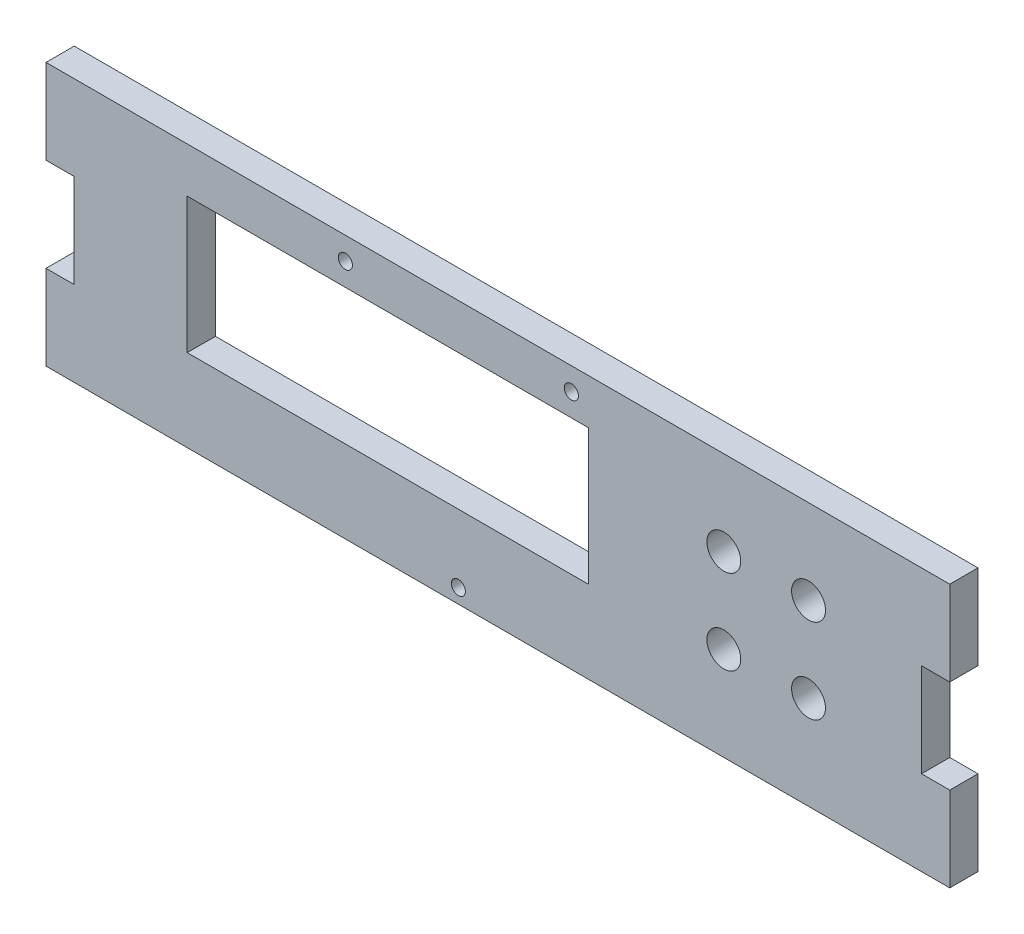
SolidWorks part; units mm, degrees
ref_plane "Plan de face" through (0, 0, 0) normal (0, 0, 1) x (1, 0, 0)
ref_plane "Plan de dessus" through (0, 0, 0) normal (0, 1, 0) x (1, 0, 0)
ref_plane "Plan de droite" through (0, 0, 0) normal (1, 0, 0) x (0, 0, -1)
sketch "Esquisse1" plane through (0, 0, 0) normal (0, 0, 1) x (1, 0, 0)
  line L0 (-79.9049, -61.6513) -> (-79.9049, -46.6513)
  line L1 (-79.9049, -46.6513) -> (80.0951, -46.6513)
  line L3 (-79.9049, -93.2213) -> (80.0951, -93.2213)
  line L5 (-79.9049, -61.6513) -> (-74.9049, -61.6513)
  line L7 (-79.9049, -78.2213) -> (-74.9049, -78.2213)
  line L8 (-74.9049, -61.6513) -> (-74.9049, -78.2213)
  line L9 (80.0951, -61.6513) -> (75.0951, -61.6513)
  line L11 (80.0951, -78.2213) -> (75.0951, -78.2213)
  line L12 (75.0951, -61.6513) -> (75.0951, -78.2213)
  line L13 (-79.9049, -78.2213) -> (-79.9049, -93.2213)
  line L14 (80.0951, -93.2213) -> (80.0951, -78.2213)
  line L15 (80.0951, -61.6513) -> (80.0951, -46.6513)
  line L17 (-54.9049, -54.6513) -> (16.0951, -54.6513)
  line L18 (-54.9049, -54.6513) -> (-54.9049, -78.6513)
  line L19 (-54.9049, -78.6513) -> (16.0951, -78.6513)
  line L20 (16.0951, -54.6513) -> (16.0951, -78.6513)
  circle A0 centre (40.0951, -61.6513) radius 3
  circle A1 centre (40.0951, -76.6513) radius 3
  circle A2 centre (55.0951, -61.6513) radius 3
  circle A3 centre (55.0951, -76.6513) radius 3
  circle A4 centre (13.0951, -50.6513) radius 1.25
  circle A5 centre (-26.9049, -50.6513) radius 1.25
  circle A6 centre (-6.9049, -90.6513) radius 1.25
  point P20 (80.0951, -54.1513)
  dimension "D1" = 6
  dimension "D9" = 6
  dimension "D10" = 6
  dimension "D11" = 6
  dimension "D22" = 2.5
  dimension "D25" = 2.5
  dimension "D28" = 2.5
  dimension "D2" = 15
  dimension "D3" = 20
  dimension "D4" = 15
  dimension "D5" = 16.57
  dimension "D6" = 15
  dimension "D7" = 15
  dimension "D8" = 16.57
  dimension "D12" = 0
  dimension "D13" = 71
  dimension "D14" = 160
  dimension "D15" = 0
  dimension "D16" = 15
  dimension "D17" = 15
  dimension "D18" = 0
  dimension "D19" = 24
  dimension "D20" = 20
  dimension "D21" = 8
  dimension "D23" = 3
  dimension "D24" = 4
  dimension "D26" = 4
  dimension "D27" = 40
  dimension "D29" = 12
  dimension "D30" = 23
extrude "Boss.-Extru.2" add sketch "Esquisse1" along normal blind 5 contours L0 L1 L15 L9 L12 L11 L14 L3 L13 L7 L8 L5
extrude "Enlèv. mat.-Extru.2" cut sketch "Esquisse1<4>" along normal blind 7 contours L19 L20 L17 L18
sketch "Esquisse1<4>" plane through (0, 0, 0) normal (0, 0, 1) x (1, 0, 0) same geometry as "Esquisse1"
extrude "Enlèv. mat.-Extru.3" cut sketch "Esquisse1<5>" along normal blind 10 contours A2 | A0 | A3 | A1 | A4 | A5 | A6
sketch "Esquisse1<5>" plane through (0, 0, 0) normal (0, 0, 1) x (1, 0, 0) same geometry as "Esquisse1"
